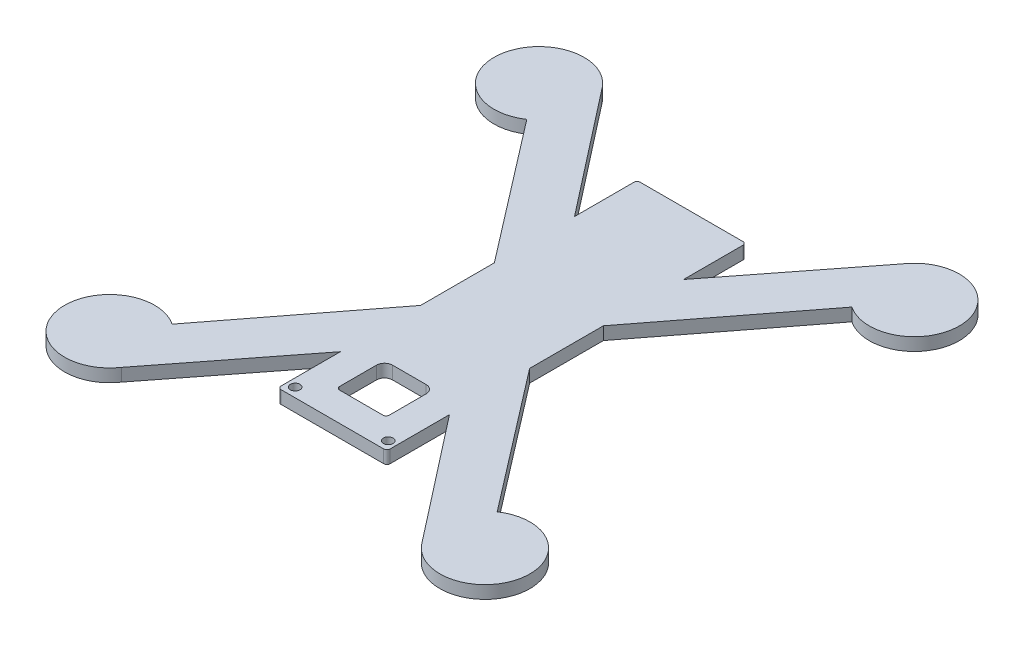
SolidWorks part; units mm, degrees
ref_plane "Front Plane" through (0, 0, 0) normal (0, 0, 1) x (1, 0, 0)
ref_plane "Top Plane" through (0, 0, 0) normal (0, 1, 0) x (1, 0, 0)
ref_plane "Right Plane" through (0, 0, 0) normal (1, 0, 0) x (0, 0, -1)
sketch "Frame Sketch" plane through (0, 0, 0) normal (0, 1, 0) x (1, 0, 0)
  line L0 (2, 0) -> (2, 126.6085) construction
  line L5 (-15, 11.5) -> (-48.6747, 55.2899)
  line L6 (-48.6747, 0) -> (67.0859, 0) construction
  line L11 (2, 0) -> (2, -105.8001) construction
  line L22 (-15, 36.5) -> (-46.0248, 76.2899)
  line L23 (-15, 56) -> (18, 56)
  line L24 (-15, 56) -> (-15, -55)
  line L25 (-14, -56) -> (19, -56)
  line L26 (19, 55) -> (19, -56)
  line L27 (-15, 56) -> (19, -56) construction
  line L28 (-15, -56) -> (19, 56) construction
  line L29 (-15, -11.5) -> (-48.6747, -55.2899)
  line L30 (-15, -36.5) -> (-15, -11.5)
  line L31 (-15, -36.5) -> (-46.0248, -76.2899)
  line L32 (-48.6747, -55.2899) -> (-46.0248, -76.2899)
  line L33 (19, -36.5) -> (19, -11.5)
  line L34 (19, -36.5) -> (50.0248, -76.2899)
  line L35 (-15, 36.5) -> (-15, 11.5)
  line L36 (-48.6747, 55.2899) -> (-46.0248, 76.2899)
  line L37 (52.6747, -55.2899) -> (50.0248, -76.2899)
  line L38 (19, -11.5) -> (52.6747, -55.2899)
  line L39 (19, 11.5) -> (52.6747, 55.2899)
  line L40 (19, 36.5) -> (19, 11.5)
  line L41 (19, 36.5) -> (50.0248, 76.2899)
  line L42 (52.6747, 55.2899) -> (50.0248, 76.2899)
  line L44 (-4.75, -47) -> (8.75, -47)
  line L45 (-5.75, -46) -> (-5.75, -34.5)
  line L46 (-3.25, -32) -> (7.25, -32)
  line L47 (9.75, -46) -> (9.75, -34.5)
  line L48 (-5.75, -47) -> (9.75, -32) construction
  line L49 (-5.75, -32) -> (9.75, -47) construction
  circle A0 centre (-56.5031, 66.9449) radius 14.04
  circle A5 centre (-56.5031, -66.9449) radius 14.04
  circle A6 centre (60.5031, -66.9449) radius 14.04
  circle A7 centre (60.5031, 66.9449) radius 14.04
  arc A8 (19, 55) -> (18, 56) centre (18, 55) ccw
  arc A9 (19, -55) -> (18, -56) centre (18, -55) cw
  arc A10 (-15, 55) -> (-14, 56) centre (-14, 55) cw
  arc A11 (-14, -56) -> (-15, -55) centre (-14, -55) cw
  circle A12 centre (-12.5, -53.1) radius 1.5
  circle A13 centre (16.5, -53.1) radius 1.5
  arc A14 (9.75, -46) -> (8.75, -47) centre (8.75, -46) cw
  arc A15 (-4.75, -47) -> (-5.75, -46) centre (-4.75, -46) cw
  arc A16 (-5.75, -34.5) -> (-3.25, -32) centre (-3.25, -34.5) cw
  arc A17 (7.25, -32) -> (9.75, -34.5) centre (7.25, -34.5) cw
  point P0 (0, 0)
  point P6 (0, 0)
  point P52 (2, -39.5)
  dimension "D6" = 1
  dimension "D7" = 2.9
  dimension "D8" = 2.5
  dimension "D11" = 9
  dimension "D12" = 9.25
  dimension "D13" = 2.5
  dimension "D14" = 2.5
  dimension "D1" = 25
  dimension "D2" = 21
  dimension "D3" = 112
  dimension "D4" = 34
  dimension "D9" = 15
  dimension "D10" = 15.5
extrude "Frame Bottom Plate" add sketch "Frame Sketch" along normal blind 4 contours L26 L23 L24 L25 | L37 A6 | L34 L37 L38 L33 | L39 L42 L41 L40 | A7 | L22 L36 L5 L35 | A0 | L29 L32 L31 L30 | A5 region at (2, 0, -2.7576) region at (61.9322, 0, 67.1253)
